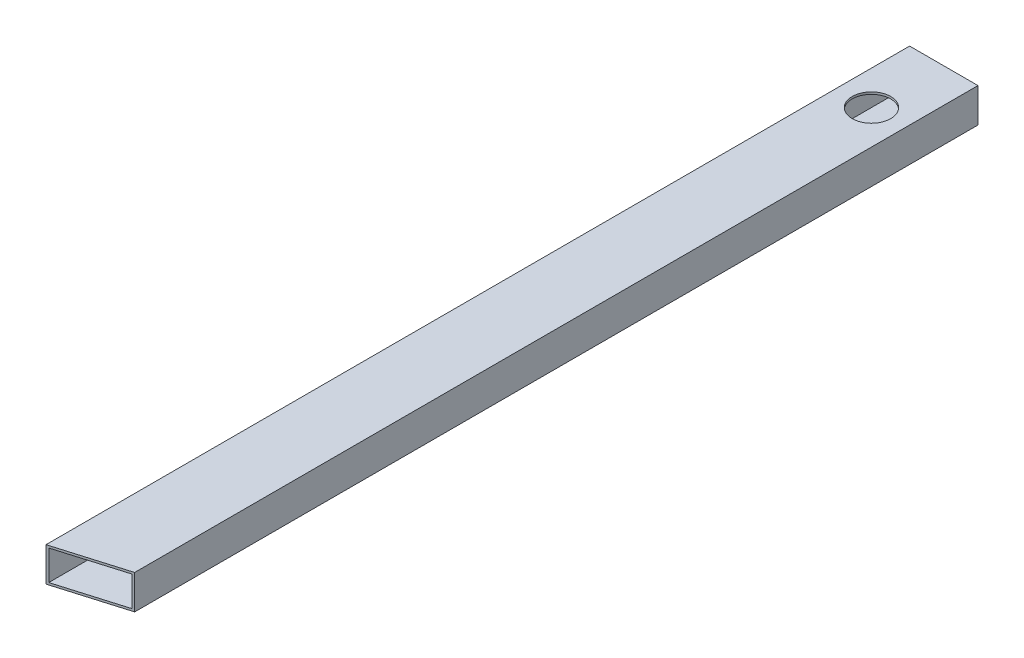
SolidWorks part; units mm, degrees
ref_plane "Front Plane" through (0, 0, 0) normal (0, 0, 1) x (1, 0, 0)
ref_plane "Top Plane" through (0, 0, 0) normal (0, 1, 0) x (1, 0, 0)
ref_plane "Right Plane" through (0, 0, 0) normal (1, 0, 0) x (0, 0, -1)
sketch "Sketch1" plane through (0, 0, 0) normal (0, 0, 1) x (1, 0, 0)
  line L0 (-23.8125, 11.1125) -> (23.8125, 11.1125)
  line L2 (-25.4, 12.7) -> (25.4, 12.7)
  line L3 (-25.4, 12.7) -> (-25.4, -12.7)
  line L4 (-25.4, -12.7) -> (25.4, -12.7)
  line L5 (25.4, 12.7) -> (25.4, -12.7)
  line L10 (23.8125, 11.1125) -> (23.8125, -11.1125)
  line L11 (-23.8125, -11.1125) -> (23.8125, -11.1125)
  line L12 (-23.8125, 11.1125) -> (-23.8125, -11.1125)
  point P12 (0, 12.7)
  point P14 (25.4, 0)
  dimension "Wall Thickness" = 1.5875
  dimension "Outside Width" = 50.8
  dimension "Outside Height" = 25.4
  dimension "Inside Height" = 22.225
  dimension "Inside Width" = 47.625
sketch "Sketch2" plane through (0, 0, 0) normal (1, 0, 0) x (0, 0, -1)
  line L0 (320.675, 0) -> (-320.675, 0)
  point P4 (0, 0)
  point P7 (-320.675, 0)
  point P10 (320.675, 0)
  dimension "Length" = 641.35
sketch "Sketch3" plane through (0, 0, 0) normal (0, 0, 1) x (1, 0, 0)
  line L21 (25.4, 12.7) -> (-25.4, 12.7)
  line L22 (25.4, -12.7) -> (25.4, 12.7)
  line L23 (-25.4, -12.7) -> (25.4, -12.7)
  line L24 (-25.4, 12.7) -> (-25.4, -12.7)
  line L25 (25.4, 12.7) -> (-25.4, 12.7)
  line L26 (25.4, -12.7) -> (25.4, 12.7)
  line L27 (-25.4, -12.7) -> (25.4, -12.7)
  line L28 (-25.4, 12.7) -> (-25.4, -12.7)
  line L29 (23.8125, 11.1125) -> (-23.8125, 11.1125)
  line L30 (23.8125, -11.1125) -> (23.8125, 11.1125)
  line L31 (-23.8125, -11.1125) -> (23.8125, -11.1125)
  line L32 (-23.8125, 11.1125) -> (-23.8125, -11.1125)
  line L33 (23.8125, 11.1125) -> (-23.8125, 11.1125)
  line L34 (23.8125, -11.1125) -> (23.8125, 11.1125)
  line L35 (-23.8125, -11.1125) -> (23.8125, -11.1125)
  line L36 (-23.8125, 11.1125) -> (-23.8125, -11.1125)
  dimension "D1" = 0
  dimension "D2" = 0
extrude "Boss-Extrude1" add sketch "Sketch3" along normal up to vertex (320.675 mm away) and the other way up to vertex (320.675 mm away) up to point (0, 0, 320.675) other way up to point (0, 0, -320.675)
sketch "Drawing Reference" plane through (0, 0, 0) normal (1, 0, 0) x (0, 0, -1)
  line L0 (-320.675, 0) -> (320.675, 0) construction
  line L1 (0, -12.7) -> (0, 12.7) construction
  line L2 (-320.675, -12.7) -> (320.675, -12.7) construction
  line L5 (-320.675, 12.7) -> (320.675, 12.7) construction
  point P7 (-284.099, 0)
  point P8 (284.099, 0)
  dimension "D1" = 36.576
sketch "Sketch4" plane through (0, 12.7, 0) normal (0, 1, 0) x (1, 0, 0)
  line L0 (-25.4, -320.675) -> (25.4, -305.6274)
  line L1 (25.4, -320.675) -> (25.4, 320.675) construction
  line L2 (25.4, -320.675) -> (-25.4, -320.675)
  dimension "D1" = 16.5
extrude "Cut-Extrude1" cut sketch "Sketch4" against normal through all and the other way through all flip side to cut
sketch "Sketch8" plane through (0, 12.7, 0) normal (0, 1, 0) x (1, 0, 0)
  line L0 (0, 320.675) -> (0, 266.954) construction
  line L1 (25.4, 320.675) -> (-25.4, 320.675) construction
  circle A0 centre (0, 266.954) radius 14.2875
  dimension "D1" = 53.721
extrude "Cut-Extrude2" cut sketch "Sketch8" against normal through all
equation "\"D1@Drawing Reference\"=\"Outside Width@Sketch1\" * 0.72"
